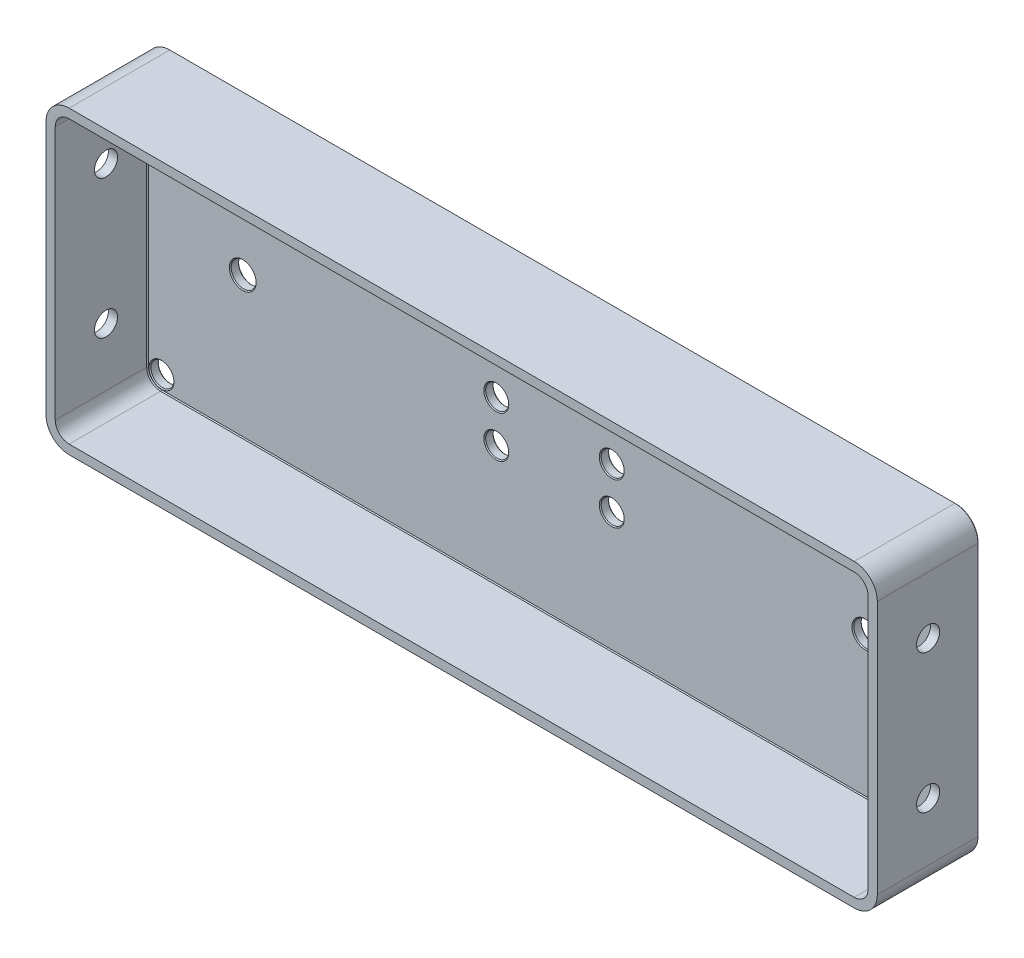
SolidWorks part; units mm, degrees
ref_plane "Front Plane" through (0, 0, 0) normal (0, 0, 1) x (1, 0, 0)
ref_plane "Top Plane" through (0, 0, 0) normal (0, 1, 0) x (1, 0, 0)
ref_plane "Right Plane" through (0, 0, 0) normal (1, 0, 0) x (0, 0, -1)
sketch "Sketch3" plane through (0, 0, 0) normal (0, 0, 1) x (1, 0, 0)
  line L0 (-15.875, 5.7326) -> (15.875, 5.7326) construction
  line L1 (107.95, -41.275) -> (-107.95, -41.275)
  line L2 (114.3, -34.925) -> (114.3, 34.925)
  line L3 (107.95, 41.275) -> (-107.95, 41.275)
  line L4 (-114.3, -34.925) -> (-114.3, 34.925)
  line L5 (114.3, -41.275) -> (-114.3, 41.275) construction
  line L6 (114.3, 41.275) -> (-114.3, -41.275) construction
  line L12 (72.898, 12.7) -> (72.898, -12.7) construction
  line L13 (72.898, -12.7) -> (98.298, -12.7) construction
  line L14 (98.298, -12.7) -> (98.298, 12.7) construction
  line L15 (98.298, 12.7) -> (72.898, 12.7) construction
  line L16 (72.898, 12.7) -> (98.298, -12.7) construction
  line L17 (98.298, 12.7) -> (72.898, -12.7) construction
  line L18 (-98.298, 12.7) -> (-72.898, 12.7) construction
  line L19 (-72.898, 12.7) -> (-72.898, -12.7) construction
  line L20 (-72.898, -12.7) -> (-98.298, -12.7) construction
  line L21 (-98.298, -12.7) -> (-98.298, 12.7) construction
  line L22 (-98.298, 12.7) -> (-72.898, -12.7) construction
  line L23 (-72.898, 12.7) -> (-98.298, -12.7) construction
  line L24 (-15.875, -5.7326) -> (15.875, 5.7326) construction
  line L25 (-15.875, 5.7326) -> (15.875, -5.7326) construction
  line L26 (15.875, 5.7326) -> (15.875, -5.7326) construction
  line L27 (15.875, -5.7326) -> (-15.875, -5.7326) construction
  line L28 (-15.875, -5.7326) -> (-15.875, 5.7326) construction
  line L29 (-15.875, 5.7326) -> (15.875, -5.7326) construction
  line L30 (15.875, 5.7326) -> (-15.875, -5.7326) construction
  arc A0 (114.3, 34.925) -> (107.95, 41.275) centre (107.95, 34.925) ccw
  arc A1 (107.95, -41.275) -> (114.3, -34.925) centre (107.95, -34.925) ccw
  arc A2 (-107.95, -41.275) -> (-114.3, -34.925) centre (-107.95, -34.925) cw
  arc A3 (-107.95, 41.275) -> (-114.3, 34.925) centre (-107.95, 34.925) ccw
  circle A8 centre (-107.95, 34.925) radius 3.175
  circle A9 centre (-107.95, -34.925) radius 3.175
  circle A10 centre (107.95, -34.925) radius 3.175
  circle A11 centre (107.95, 34.925) radius 3.175
  circle A24 centre (-85.598, 0) radius 3.429
  circle A25 centre (85.598, 0) radius 3.429
  circle A26 centre (-15.875, 5.7326) radius 3.175
  circle A27 centre (15.875, 5.7326) radius 3.175
  circle A28 centre (15.875, -5.7326) radius 3.175
  circle A29 centre (-15.875, -5.7326) radius 3.175
  point P0 (0, 0)
  point P22 (-114.3, 0)
  point P23 (0, 0)
  point P57 (-98.298, 0)
  dimension "D3" = 6.35
  dimension "D6" = 16.002
  dimension "D7" = 6.35
  dimension "D8" = 16.002
  dimension "D9" = 28.575
  dimension "D10" = 31.75
  dimension "D11" = 6.35
  dimension "D14" = 25.4
  dimension "D4" = 6.858
  dimension "D5" = 6.858
  dimension "D1" = 82.55
  dimension "D2" = 228.6
  dimension "D12" = 25.4
extrude "Boss-Extrude1" add sketch "Sketch3" along normal blind 27.94
sketch "Sketch4" plane through (0, 0, 27.94) normal (0, 0, 1) x (1, 0, 0)
  line L0 (107.95, 38.735) -> (-107.95, 38.735)
  line L1 (-111.76, 34.925) -> (-111.76, -34.925)
  line L2 (-107.95, -38.735) -> (107.95, -38.735)
  line L3 (111.76, -34.925) -> (111.76, 34.925)
  line L4 (107.95, 41.275) -> (-107.95, 41.275)
  line L5 (-114.3, 34.925) -> (-114.3, -34.925)
  line L6 (-107.95, -41.275) -> (107.95, -41.275)
  line L7 (114.3, -34.925) -> (114.3, 34.925)
  line L8 (107.95, 41.275) -> (-107.95, 41.275)
  line L9 (-114.3, 34.925) -> (-114.3, -34.925)
  line L10 (-107.95, -41.275) -> (107.95, -41.275)
  line L11 (114.3, -34.925) -> (114.3, 34.925)
  arc A0 (111.76, 34.925) -> (107.95, 38.735) centre (107.95, 34.925) ccw
  arc A1 (-107.95, 38.735) -> (-111.76, 34.925) centre (-107.95, 34.925) ccw
  arc A2 (-111.76, -34.925) -> (-107.95, -38.735) centre (-107.95, -34.925) ccw
  arc A3 (107.95, -38.735) -> (111.76, -34.925) centre (107.95, -34.925) ccw
  arc A4 (114.3, 34.925) -> (107.95, 41.275) centre (107.95, 34.925) ccw
  arc A5 (-107.95, 41.275) -> (-114.3, 34.925) centre (-107.95, 34.925) ccw
  arc A6 (-114.3, -34.925) -> (-107.95, -41.275) centre (-107.95, -34.925) ccw
  arc A7 (107.95, -41.275) -> (114.3, -34.925) centre (107.95, -34.925) ccw
  arc A8 (114.3, 34.925) -> (107.95, 41.275) centre (107.95, 34.925) ccw
  arc A9 (-107.95, 41.275) -> (-114.3, 34.925) centre (-107.95, 34.925) ccw
  arc A10 (-114.3, -34.925) -> (-107.95, -41.275) centre (-107.95, -34.925) ccw
  arc A11 (107.95, -41.275) -> (114.3, -34.925) centre (107.95, -34.925) ccw
  dimension "D1" = 0
  dimension "D2" = 2.54
extrude "Cut-Extrude1" cut sketch "Sketch4" against normal blind 25.4 contours A0 L0 A1 L1 A2 L2 A3 L3
chamfer "Chamfer1" distance 0.254 angle 45 18 edges at (111.125, 34.925, 0) (111.125, -34.925, 0) (-104.775, -34.925, 0) (-104.775, 34.925, 0) (89.027, 0, 0) (-82.169, 0, 0) (0, 41.275, 0) (-112.4401, 39.4151, 0) (-114.3, 0, 0) (-112.4401, -39.4151, 0) (0, -41.275, 0) (112.4401, -39.4151, 0) (114.3, 0, 0) (112.4401, 39.4151, 0) (-12.7, -5.7326, 0) (19.05, -5.7326, 0) (19.05, 5.7326, 0) (-12.7, 5.7326, 0)
chamfer "Chamfer2" distance 0.254 angle 45 18 edges at (110.6441, -37.6191, 2.54) (0, -38.735, 2.54) (-110.6441, -37.6191, 2.54) (-111.76, 0, 2.54) (-110.6441, 37.6191, 2.54) (0, 38.735, 2.54) (110.6441, 37.6191, 2.54) (111.76, 0, 2.54) (111.125, 34.925, 2.54) (111.125, -34.925, 2.54) (-104.775, -34.925, 2.54) (-104.775, 34.925, 2.54) (89.027, 0, 2.54) (-82.169, 0, 2.54) (-12.7, -5.7326, 2.54) (19.05, -5.7326, 2.54) (19.05, 5.7326, 2.54) (-12.7, 5.7326, 2.54)
sketch "Sketch5" plane through (114.3, 0, 0) normal (1, 0, 0) x (0, 0, -1)
  line L0 (-13.97, 19.177) -> (-13.97, -18.923) construction
  line L1 (-27.94, -34.925) -> (-27.94, 34.925) construction
  line L4 (-27.94, -41.275) -> (-0.254, -41.275) construction
  circle A0 centre (-13.97, 19.177) radius 3.175
  circle A1 centre (-13.97, -18.923) radius 3.175
  dimension "D1" = 6.35
  dimension "D2" = 38.1
  dimension "D3" = 13.97
  dimension "D4" = 22.352
extrude "Cut-Extrude2" cut sketch "Sketch5" against normal through all
